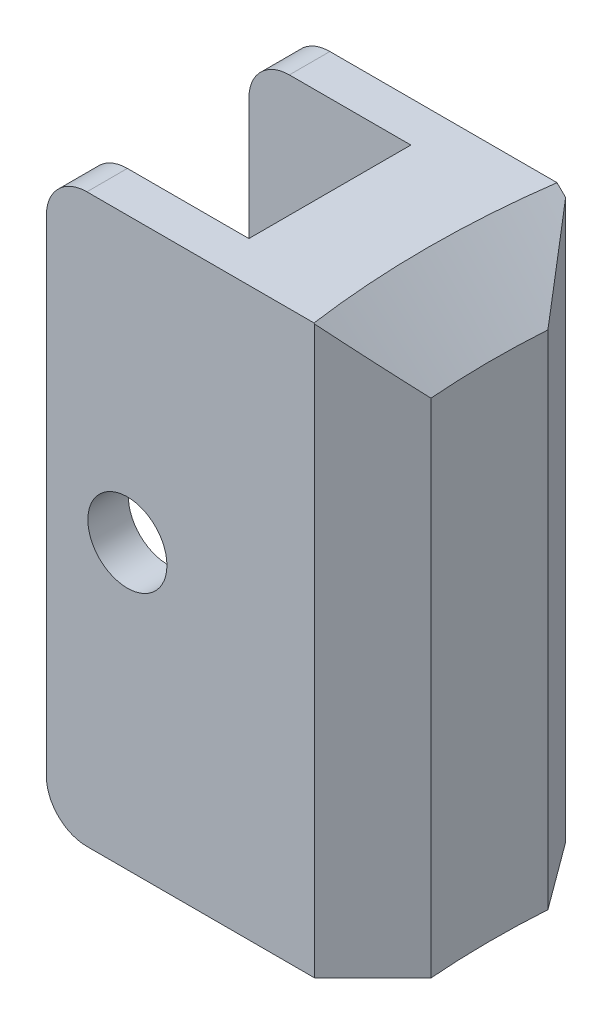
SolidWorks part; units mm, degrees
ref_plane "Front Plane" through (0, 0, 0) normal (0, 0, 1) x (1, 0, 0)
ref_plane "Top Plane" through (0, 0, 0) normal (0, 1, 0) x (1, 0, 0)
ref_plane "Right Plane" through (0, 0, 0) normal (1, 0, 0) x (0, 0, -1)
sketch "Sketch1" plane through (0, 0, 0) normal (0, 0, 1) x (1, 0, 0)
  line L0 (-44.45, 11.1125) -> (-44.45, -11.1125)
  line L1 (-44.45, -11.1125) -> (-28.575, -11.1125)
  line L2 (-28.575, 0) -> (0, 0) construction
  line L4 (-28.575, -11.1125) -> (-28.575, 11.1125)
  line L5 (-28.575, 11.1125) -> (-44.45, 11.1125)
  line L8 (0, -988.495) -> (0, 49011.505) construction
  line L9 (-38.1, 11.1125) -> (-38.1, -11.1125) construction
  point P7 (-50.8, -11.1125)
  dimension "D1" = 101.6
  dimension "D2" = 22.225
  dimension "D3" = 9.525
  dimension "D4" = 6.35
  dimension "D7" = 12.7
extrude "Boss-Extrude1" add sketch "Sketch1" along normal mid plane 9.525
sketch "Sketch2" plane through (0, 0, 0) normal (0, 0, 1) x (1, 0, 0)
  line L1 (-38.1, 11.1125) -> (-38.1, -11.1125)
  line L2 (0, 0) -> (-38.1, 0) construction
  line L5 (-44.45, -11.1125) -> (-44.45, 11.1125)
  line L6 (-38.1, 11.1125) -> (-44.45, 11.1125)
  line L8 (-44.45, 11.1125) -> (-44.45, -11.1125) construction
  line L12 (-38.1, 200011.1125) -> (-38.1, -200011.1125) construction
  line L14 (-38.1, -11.1125) -> (-44.45, -11.1125)
  line L15 (-44.45, -11.1125) -> (-28.575, -11.1125) construction
  line L16 (-28.575, 11.1125) -> (-44.45, 11.1125) construction
extrude "Cut-Extrude1" cut sketch "Sketch2" against normal mid plane 6.35
sketch "Sketch3" plane through (0, 11.1125, 0) normal (0, 1, 0) x (1, 0, 0)
  circle A0 centre (0, 0) radius 31.75
  dimension "D1" = 63.5
extrude "Cut-Extrude2" cut sketch "Sketch3" against normal through all
chamfer "Chamfer1" distance 2.54 angle 45 3 edges at (-31.75, 11.1125, 0) (-31.3908, 0, -4.7625) (-31.3908, 0, 4.7625)
sketch "Sketch4" plane through (0, 0, 4.7625) normal (0, 0, 1) x (1, 0, 0)
  line L1 (5.2388, 0) -> (-5.2388, 0) construction
  circle A0 centre (-41.275, 0) radius 1.55
  dimension "D2" = 3.1
  dimension "D3" = 9.525
extrude "Cut-Extrude3" cut sketch "Sketch4" against normal through all
fillet "Fillet1" radius 1.5875 4 edges at (-44.45, -11.1125, -3.9688) (-44.45, -11.1125, 3.9688) (-44.45, 11.1125, -3.9688) (-44.45, 11.1125, 3.9688)
